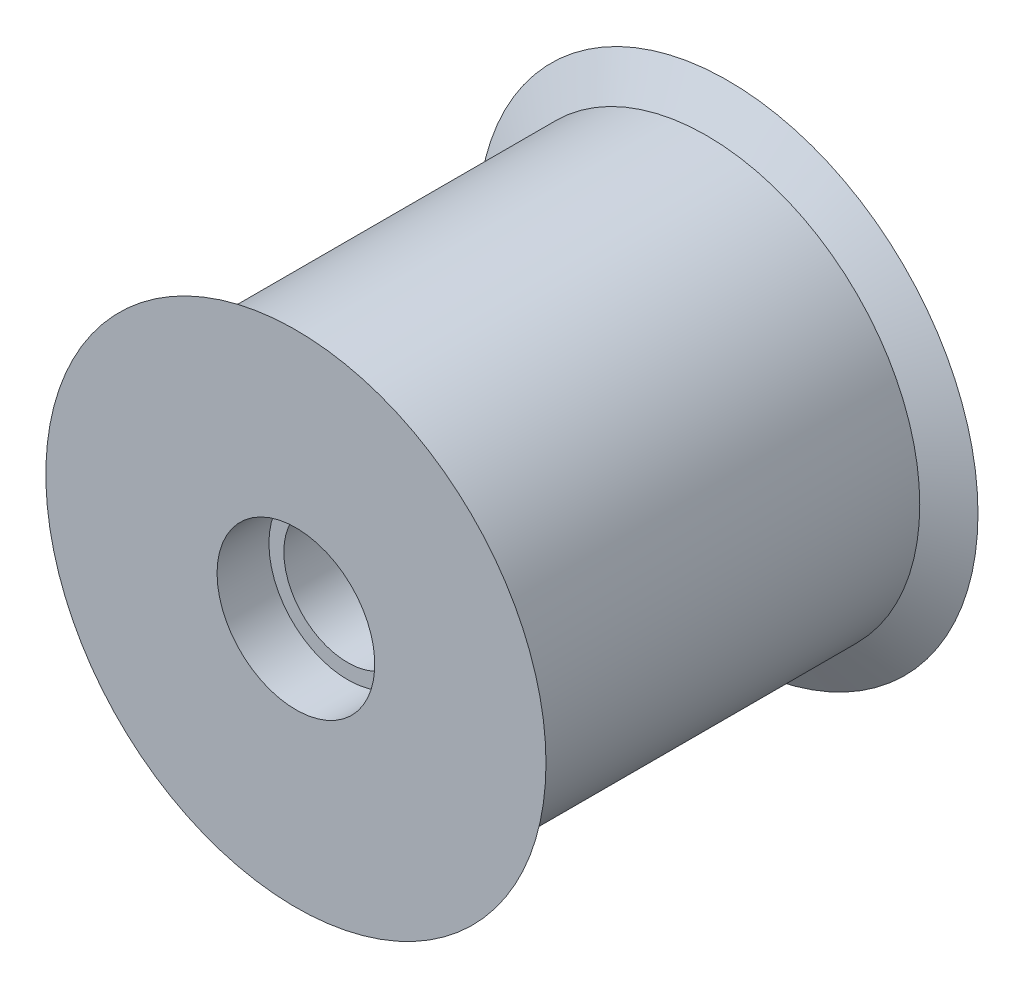
SolidWorks part; units mm, degrees
ref_plane "Front Plane" through (0, 0, 0) normal (0, 0, 1) x (1, 0, 0)
ref_plane "Top Plane" through (0, 0, 0) normal (0, 1, 0) x (1, 0, 0)
ref_plane "Right Plane" through (0, 0, 0) normal (1, 0, 0) x (0, 0, -1)
sketch "Sketch1" plane through (0, 0, 0) normal (0, 1, 0) x (1, 0, 0)
  line L0 (0, 0) -> (0, 60.8)
  line L3 (0, 60.8) -> (-36, 60.8)
  line L4 (-30, 3) -> (-36, 3)
  line L5 (-36, 3) -> (-36, 0)
  line L6 (-30, 57.8) -> (-30, 3)
  line L7 (-30, 57.8) -> (-36, 57.8)
  line L8 (-36, 57.8) -> (-36, 60.8)
  line L9 (-36, 0) -> (0, 0)
  line L10 (-36, 57.8) -> (-36, 3) construction
  dimension "D1" = 54.8
  dimension "D2" = 6
  dimension "D3" = 3
  dimension "D7" = 30
revolve "Revolve1" add sketch "Sketch1" angle 360 about L0
sketch "Sketch7" plane through (0, 0, 0) normal (0, 1, 0) x (1, 0, 0)
  line L0 (0, 0) -> (0, 64.211) construction
  line L1 (0, 60.8) -> (-11.1, 60.8)
  line L2 (-11.1, 60.8) -> (-11.1, 53.5)
  line L3 (-11.1, 53.5) -> (-9, 53.5)
  line L4 (-9, 53.5) -> (-9, 7.3)
  line L5 (-9, 7.3) -> (-11.1, 7.3)
  line L6 (-11.1, 7.3) -> (-11.1, 0)
  line L7 (-11.1, 0) -> (0, 0)
  line L8 (-11.1, 53.5) -> (-11.1, 7.3) construction
  line L9 (-36, 0) -> (36, 0) construction
  line L10 (36, 60.8) -> (-36, 60.8) construction
  line L11 (0, 60.8) -> (0, 0)
  dimension "D1" = 11.1
  dimension "D2" = 9
  dimension "D3" = 7.3
  dimension "D4" = 7.3
revolve "Cut-Revolve1" cut sketch "Sketch7" angle 360 about L11
ref_plane "Plane1" through (0, 0, -30.4) normal (0, 0, 1) x (1, 0, 0)
chamfer "Chamfer1" distance 6 angle 30 2 edges at (36, 0, -57.8) (36, 0, -3)
